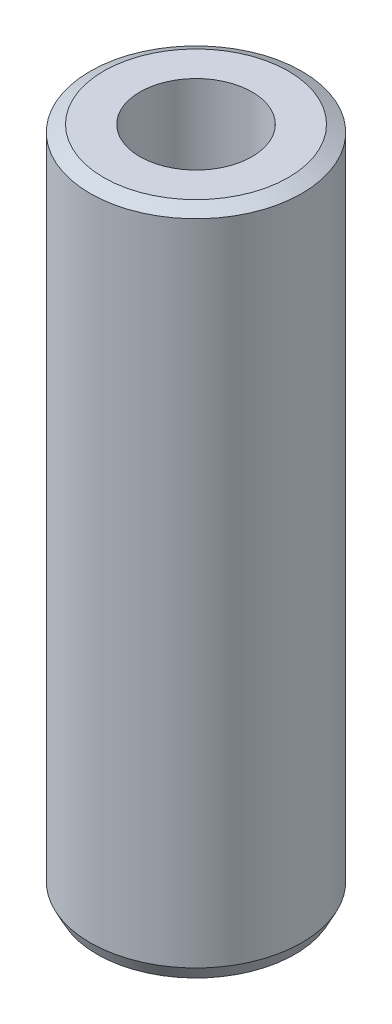
SolidWorks part; units mm, degrees
ref_plane "Front Plane" through (0, 0, 0) normal (0, 0, 1) x (1, 0, 0)
ref_plane "Top Plane" through (0, 0, 0) normal (0, 1, 0) x (1, 0, 0)
ref_plane "Right Plane" through (0, 0, 0) normal (1, 0, 0) x (0, 0, -1)
sketch "Sketch1" plane through (0, 0, 0) normal (0, 1, 0) x (1, 0, 0)
  circle A0 centre (0, 0) radius 20
  dimension "SHAFT_OD" = 40
extrude "Boss-Extrude1" add sketch "Sketch1" along normal blind 126.4493
sketch "Sketch2" plane through (0, 0, 0) normal (0, 1, 0) x (1, 0, 0)
  circle A0 centre (0, 0) radius 10.5961
  dimension "BORE_D" = 21.1921
extrude "Cut-Extrude1" cut sketch "Sketch2" along normal through all
chamfer "Chamfer1" distance 1.3122 angle 62.909 2 edges at (0, 126.4493, 20) (0, 0, 20) first distance on face at (0, 126.4493, 20) first distance on face at (0, 0, 10.5961)
